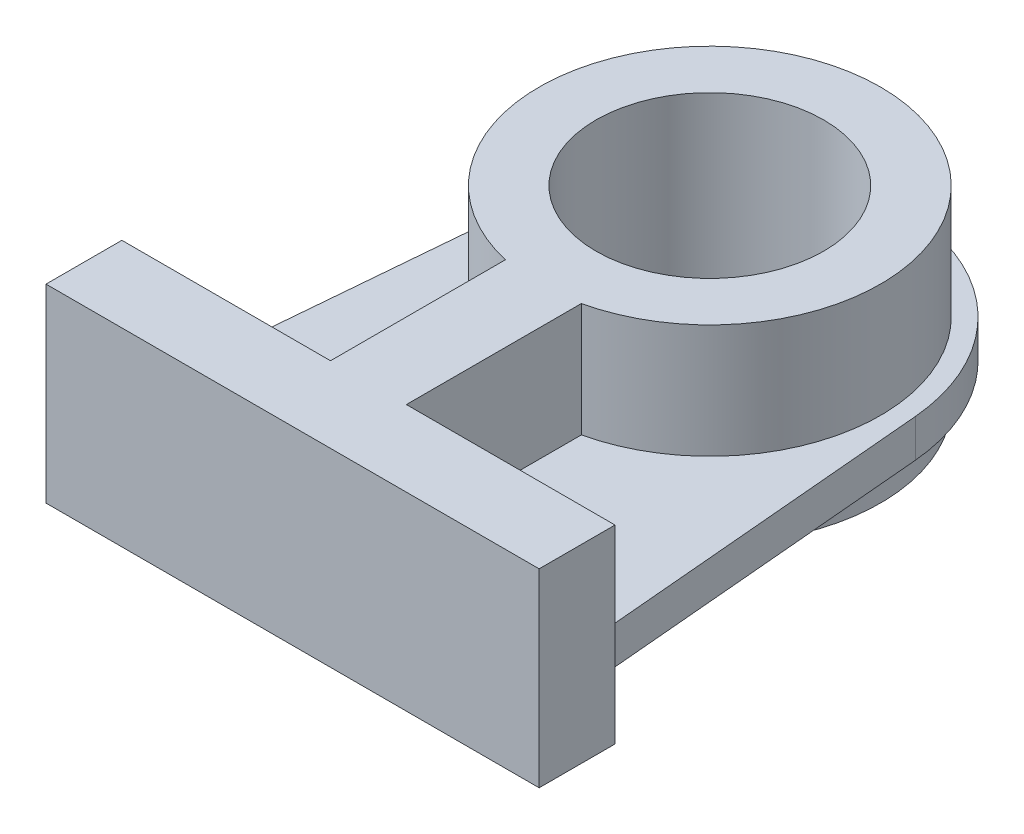
SolidWorks part; units mm, degrees
note: The reader was unsure of these and kept them because the rebuilt part matched: shared geometry of "Sketch1<3>".
ref_plane "Front Plane" through (0, 0, 0) normal (0, 0, 1) x (1, 0, 0)
ref_plane "Top Plane" through (0, 0, 0) normal (0, 1, 0) x (1, 0, 0)
ref_plane "Right Plane" through (0, 0, 0) normal (1, 0, 0) x (0, 0, -1)
sketch "Sketch1" plane through (0, 0, 0) normal (0, 1, 0) x (1, 0, 0)
  line L0 (-24.9049, 2.1789) -> (-29.0325, -45)
  line L1 (-5, 5) -> (5, 5)
  line L2 (-5, 5) -> (-5, -50)
  line L3 (-5, -50) -> (5, -50)
  line L4 (5, 5) -> (5, -50)
  line L5 (-5, 5) -> (5, -50) construction
  line L6 (-5, -50) -> (5, 5) construction
  line L7 (32.5, -55) -> (-32.5, -55)
  line L8 (32.5, -55) -> (32.5, -45)
  line L9 (32.5, -45) -> (-32.5, -45)
  line L10 (-32.5, -55) -> (-32.5, -45)
  line L11 (32.5, -55) -> (-32.5, -45) construction
  line L12 (32.5, -45) -> (-32.5, -55) construction
  line L13 (0, -22.5) -> (0, 5) construction
  line L14 (24.9049, 2.1789) -> (29.0325, -45)
  circle A0 centre (0, 0) radius 15
  circle A1 centre (0, 0) radius 22.5
  arc A2 (-5, -24.4949) -> (5, -24.4949) centre (0, 0) ccw
  arc A3 (24.9049, 2.1789) -> (-24.9049, 2.1789) centre (0, 0) ccw
  point P4 (0, -22.5)
  point P9 (0, -50)
  dimension "D2" = 45
  dimension "D3" = 30
  dimension "D4" = 50
  dimension "D1" = 85
  dimension "D5" = 10
  dimension "D6" = 10
  dimension "D7" = 55
  dimension "D8" = 65
extrude "Boss-Extrude1" add sketch "Sketch1" along normal blind 25 contours L4 A1 L2 A0 | L2 A1 L4 A0 | A1 L2 L9 L4 | L4 L9 L2 L3 | L10 L7 L8 L9 L4 L3 L2 | L2 A2 L4 A1
extrude "Boss-Extrude2" add sketch "Sketch1<3>" along normal blind 5 from offset 5 contours L14 A3 L0 L9 L2 A1 L4
sketch "Sketch1<3>" plane through (0, 0, 0) normal (0, 1, 0) x (1, 0, 0) same geometry as "Sketch1"
